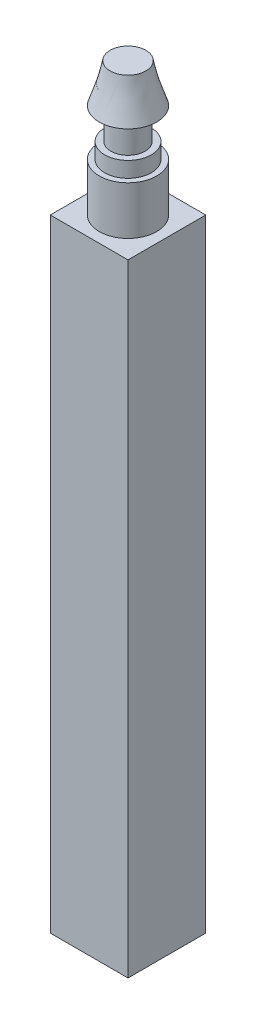
SolidWorks part; units mm, degrees
ref_plane "Front Plane" through (0, 0, 0) normal (0, 0, 1) x (1, 0, 0)
ref_plane "Top Plane" through (0, 0, 0) normal (0, 1, 0) x (1, 0, 0)
ref_plane "Right Plane" through (0, 0, 0) normal (1, 0, 0) x (0, 0, -1)
sketch "Sketch1" plane through (0, 0, 0) normal (0, 1, 0) x (1, 0, 0)
  circle A0 centre (0, 0) radius 1.85
  dimension "D1" = 3.7
extrude "Boss-Extrude1" add sketch "Sketch1" along normal blind 3.1
sketch "Sketch2" plane through (0, 3.1, 0) normal (0, 1, 0) x (1, 0, 0)
  circle A0 centre (0, 0) radius 1.5
  dimension "D1" = 3
extrude "Boss-Extrude2" add sketch "Sketch2" along normal blind 1
sketch "Sketch3" plane through (0, 4.1, 0) normal (0, 1, 0) x (1, 0, 0)
  circle A0 centre (0, 0) radius 1.1
  dimension "D1" = 2.2
extrude "Boss-Extrude3" add sketch "Sketch3" along normal blind 2
sketch "Sketch4" plane through (0, 6.1, 0) normal (0, 1, 0) x (1, 0, 0)
  circle A0 centre (0, 0) radius 1.85
  dimension "D1" = 3.7
ref_plane "Plane1" through (0, 8.6, 0) normal (0, 1, 0) x (1, 0, 0)
sketch "Sketch5" plane through (0, 8.6, 0) normal (0, 1, 0) x (1, 0, 0)
  circle A0 centre (0, 0) radius 1.15
  dimension "D1" = 2.3
loft "Loft1" add profiles "Sketch4", "Sketch5" connector at (0, 6.1, 1.85) connector at (0.6205, 8.6, 0.9683)
sketch "Sketch6" plane through (0, 0, 0) normal (0, -1, 0) x (1, 0, 0)
  line L1 (-2.5, 2.5) -> (2.5, 2.5)
  line L2 (-2.5, 2.5) -> (-2.5, -2.5)
  line L3 (-2.5, -2.5) -> (2.5, -2.5)
  line L4 (2.5, 2.5) -> (2.5, -2.5)
  line L5 (-2.5, 2.5) -> (2.5, -2.5) construction
  line L6 (-2.5, -2.5) -> (2.5, 2.5) construction
  point P0 (0, 0)
  dimension "D1" = 5
  dimension "D2" = 5
extrude "Boss-Extrude4" add sketch "Sketch6" along normal blind 40
sketch "Sketch7" plane through (0, -40, 0) normal (0, -1, 0) x (1, 0, 0)
  circle A0 centre (0, 0) radius 1
  dimension "D1" = 2
extrude "Cut-Extrude1" cut sketch "Sketch7" against normal blind 24
